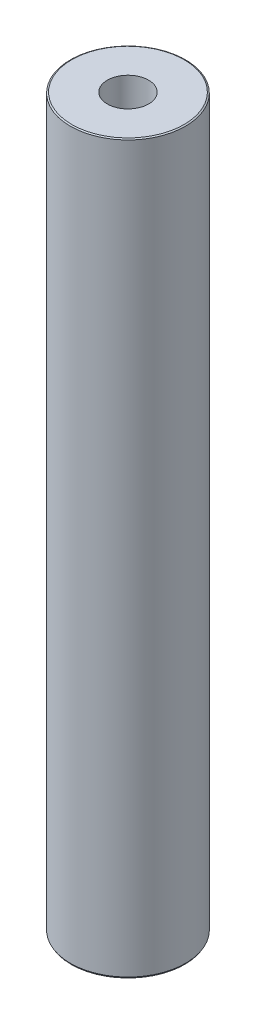
SolidWorks part; units mm, degrees
ref_plane "Front Plane" through (0, 0, 0) normal (0, 0, 1) x (1, 0, 0)
ref_plane "Top Plane" through (0, 0, 0) normal (0, 1, 0) x (1, 0, 0)
ref_plane "Right Plane" through (0, 0, 0) normal (1, 0, 0) x (0, 0, -1)
sketch "Sketch1" plane through (0, 0, 0) normal (0, 1, 0) x (1, 0, 0)
  circle A0 centre (0, 0) radius 47.5
  dimension "SHAFT_OD" = 95
extrude "Boss-Extrude1" add sketch "Sketch1" along normal blind 600
sketch "Sketch2" plane through (0, 0, 0) normal (0, 1, 0) x (1, 0, 0)
  circle A0 centre (0, 0) radius 17.0578
  dimension "BORE_D" = 34.1155
extrude "Cut-Extrude1" cut sketch "Sketch2" along normal through all
chamfer "Chamfer1" distance 0.657 angle 60 2 edges at (0, 600, 47.5) (0, 0, 47.5) first distance on face at (0, 600, 47.5) first distance on face at (0, 0, 17.0578)
